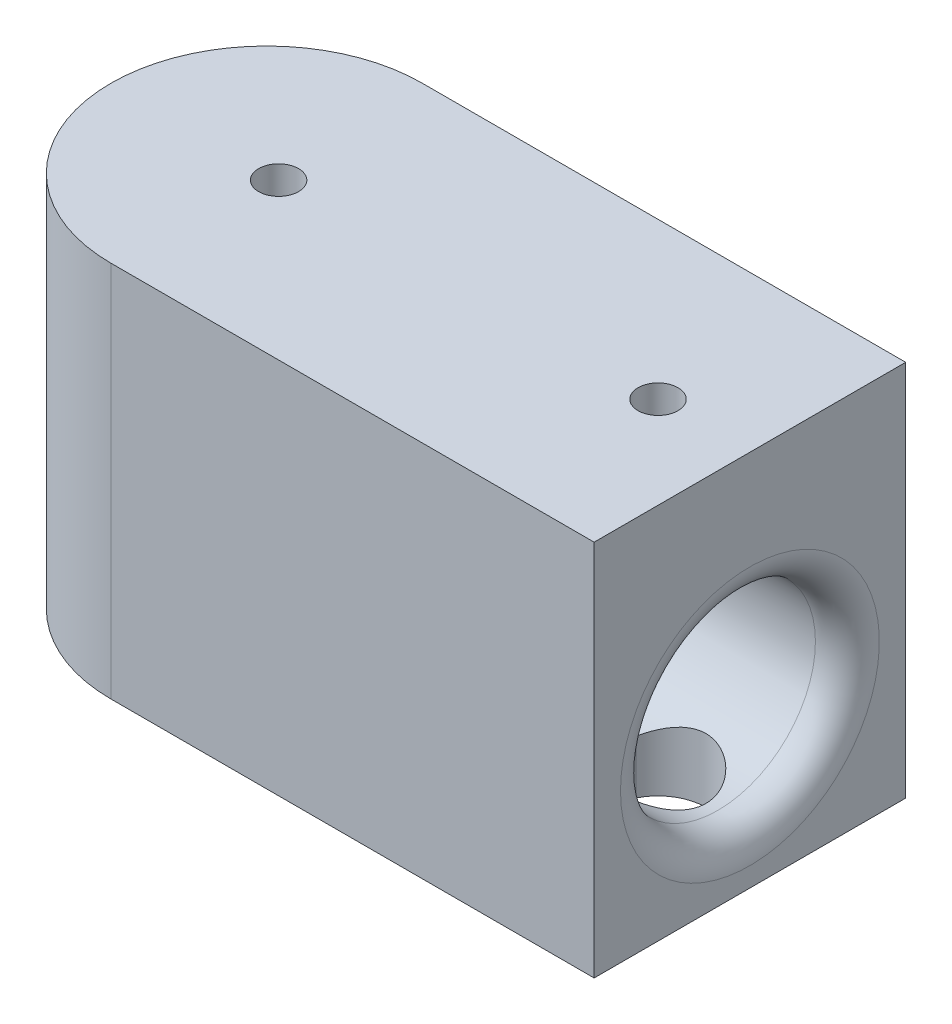
SolidWorks part; units mm, degrees
ref_plane "Front Plane" through (0, 0, 0) normal (0, 0, 1) x (1, 0, 0)
ref_plane "Top Plane" through (0, 0, 0) normal (0, 1, 0) x (1, 0, 0)
ref_plane "Right Plane" through (0, 0, 0) normal (1, 0, 0) x (0, 0, -1)
sketch "Sketch1" plane through (0, 0, 0) normal (0, 1, 0) x (1, 0, 0)
  line L1 (0, 0) -> (40, 0)
  line L2 (0, 0) -> (0, 19.5)
  line L3 (0, 19.5) -> (40, 19.5)
  line L4 (40, 0) -> (40, 19.5)
  dimension "D1" = 19.5
  dimension "D2" = 40
extrude "Boss-Extrude1" add sketch "Sketch1" along normal blind 23.625
sketch "Sketch2" plane through (40, 0, 0) normal (1, 0, 0) x (0, 0, -1)
  line L0 (9.75, 23.625) -> (9.75, 9.3125)
  line L1 (0, 23.625) -> (19.5, 23.625) construction
  circle A0 centre (9.75, 9.3125) radius 6.1
  dimension "D2" = 12.2
  dimension "D1" = 14.3125
extrude "Cut-Extrude1" cut sketch "Sketch2" against normal blind 36.25 contours A0 region at (40, 5.1211, -5.5586)
sketch "Sketch3" plane through (3.75, 0, 0) normal (1, 0, 0) x (0, 0, -1)
  circle A0 centre (9.75, 9.3125) radius 5
extrude "Cut-Extrude2" cut sketch "Sketch3" against normal up to next
sketch "Sketch5" plane through (0, 0, 0) normal (0, -1, 0) x (1, 0, 0)
  line L0 (40, -9.75) -> (34.25, -9.75)
  line L1 (40, 0) -> (40, -19.5) construction
  line L2 (34.25, -9.75) -> (10.5, -9.75)
  circle A0 centre (34.25, -9.75) radius 3
  circle A1 centre (10.5, -9.75) radius 3
  dimension "D3" = 6
  dimension "D4" = 6
  dimension "D1" = 5.75
  dimension "D2" = 23.75
extrude "Cut-Extrude3" cut sketch "Sketch5" against normal blind 18 contours A1 | L2 A0 L0 | L0 A0 L2 region at (34.25, 0, -11.0232) region at (34.25, 0, -8.4768) region at (7.5849, 0, -9.75)
sketch "Sketch6" plane through (0, 18, 0) normal (0, -1, 0) x (1, 0, 0)
  circle A0 centre (10.5, -9.75) radius 1.25
  circle A1 centre (34.25, -9.75) radius 1.25
extrude "Cut-Extrude4" cut sketch "Sketch6" against normal up to next
sketch "Sketch7" plane through (0, 0, 0) normal (0, -1, 0) x (1, 0, 0)
  line L0 (34.25, -9.75) -> (34.25, -3)
  line L1 (34.25, -3) -> (20, -3)
  line L2 (34.25, -9.75) -> (10.5, -9.75)
  circle A0 centre (20, -3) radius 1.25
  circle A1 centre (20, -16.5) radius 1.25
  dimension "D1" = 6.75
  dimension "D2" = 14.25
extrude "Cut-Extrude5" cut sketch "Sketch7" against normal blind 6.75 contours A0 | A1 region at (18.7854, 0, -3) region at (20, 0, -16.5)
fillet "Fillet1" radius 2 1 edges at (40, 9.3125, -15.85)
fillet "Fillet2" radius 9.75 2 edges at (0, 11.8125, 0) (0, 11.8125, -19.5)
sketch "Sketch8" plane through (0, 0, 0) normal (0, -1, 0) x (1, 0, 0)
  line L0 (34.25, -9.75) -> (30.25, -9.75)
  circle A0 centre (30.25, -9.75) radius 1.25
  circle M4 centre (34.25, -9.75) radius 3
  dimension "D2" = 2.5
  dimension "D1" = 4
extrude "Cut-Extrude6" cut sketch "Sketch8" against normal blind 5 contours A0 M4 region at (30.1983, 0, -9.75)
fillet "Fillet3" radius 0.5 2 edges at (31.3203, 1.6234, -9.1043) (31.3203, 1.6234, -10.3957)
